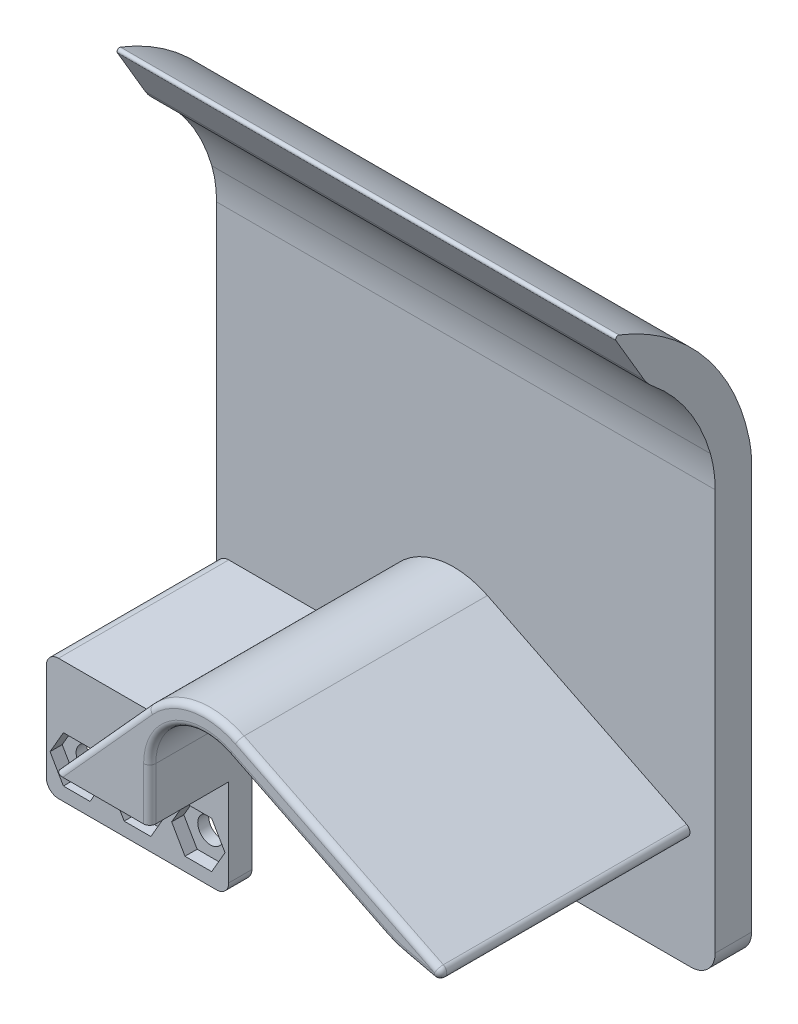
SolidWorks part; units mm, degrees
ref_plane "Front Plane" through (0, 0, 0) normal (0, 0, 1) x (1, 0, 0)
ref_plane "Top Plane" through (0, 0, 0) normal (0, 1, 0) x (1, 0, 0)
ref_plane "Right Plane" through (0, 0, 0) normal (1, 0, 0) x (0, 0, -1)
sketch "Sketch1" plane through (0, 0, 0) normal (0, 0, 1) x (1, 0, 0)
  line L0 (-31.75, -11.43) -> (-11.43, -11.43)
  line L1 (0, 0) -> (0, -50000) construction
  line L2 (-31.75, -11.43) -> (-11.7718, 10.6508)
  line L3 (31.75, -11.43) -> (11.7718, 10.6508)
  line L4 (-11.43, 0) -> (-11.43, -11.43)
  line L5 (11.43, 0) -> (11.43, -11.43)
  line L6 (11.43, -11.43) -> (31.75, -11.43)
  arc A0 (11.43, 0) -> (-11.43, 0) centre (0, 0) ccw
  arc A1 (11.7718, 10.6508) -> (-11.7718, 10.6508) centre (0, 0) ccw
  point P1 (0, 15.875)
  point P7 (0, -11.43)
  dimension "D1" = 22.86
  dimension "D2" = 31.75
  dimension "D3" = 63.5
extrude "Boss-Extrude1" add sketch "Sketch1" along normal blind 8.89
sketch "Sketch11" plane through (0, 0, 0) normal (0, 0, -1) x (-1, 0, 0)
  line L0 (11.7718, 10.6508) -> (31.75, -11.43) construction
  line L1 (31.75, -11.43) -> (11.43, -11.43) construction
  line L2 (11.43, -11.43) -> (11.43, 0) construction
  line L6 (27.1537, -6.35) -> (31.75, -11.43)
  line L7 (31.75, -11.43) -> (11.43, -11.43)
  line L13 (11.43, -6.35) -> (27.1537, -6.35)
  line L15 (11.43, -6.35) -> (11.43, -11.43)
  dimension "D1" = 5.08
extrude "Boss-Extrude2" add sketch "Sketch11" along normal blind 38.1
sketch "Sketch15" plane through (0, 0, 8.89) normal (0, 0, 1) x (1, 0, 0)
  line L1 (0, 22.5754) -> (41.9077, 22.5754)
  line L2 (0, 22.5754) -> (0, -20.5957)
  line L3 (0, -20.5957) -> (41.9077, -20.5957)
  line L4 (41.9077, 22.5754) -> (41.9077, -20.5957)
extrude "Cut-Extrude2" cut sketch "Sketch15" against normal blind 97.536
sketch "Sketch16" plane through (0, 0, 0) normal (0, 0, -1) x (-1, 0, 0)
  line L0 (11.7718, 10.6508) -> (27.1537, -6.35) construction
  line L1 (27.1537, -6.35) -> (11.43, -6.35) construction
  line L2 (0, 15.875) -> (0, 11.43) construction
  line L3 (11.7718, 10.6508) -> (27.1537, -6.35)
  line L4 (27.1537, -6.35) -> (11.43, -6.35)
  line L5 (0, 15.875) -> (0, 11.43)
  line L6 (11.43, -6.35) -> (11.43, 0)
  arc A0 (11.7718, 10.6508) -> (0, 15.875) centre (0, 0) ccw construction
  arc A1 (11.43, 0) -> (0, 11.43) centre (0, 0) ccw construction
  arc A2 (11.7718, 10.6508) -> (0, 15.875) centre (0, 0) ccw
  arc A3 (11.43, 0) -> (0, 11.43) centre (0, 0) ccw
extrude "Boss-Extrude5" add sketch "Sketch16" along normal blind 12.7
sketch "Sketch18" plane through (0, -6.35, 0) normal (0, 1, 0) x (1, 0, 0)
  line L0 (-11.43, 38.1) -> (-11.43, 12.7) construction
  line L1 (-11.43, 12.7) -> (-49.53, 12.7)
  line L2 (-11.43, 12.7) -> (-11.43, 38.1)
  line L3 (-11.43, 38.1) -> (-49.53, 38.1)
  line L4 (-49.53, 12.7) -> (-49.53, 38.1)
  line L5 (-27.1537, 38.1) -> (-11.43, 38.1) construction
  line L6 (-11.43, -8.89) -> (-11.43, 38.1) construction
  dimension "D1" = 38.1
extrude "Boss-Extrude6" add sketch "Sketch18" against normal up to surface (5.08 mm away) up to face at (-21.59, -11.43, -14.605)
sketch "Sketch17" plane through (0, -6.35, 0) normal (0, 1, 0) x (1, 0, 0)
  line L0 (-11.43, 38.1) -> (-11.43, 12.7) construction
  line L1 (-49.53, 38.1) -> (-11.43, 38.1) construction
  circle A0 centre (-15.24, 25.4) radius 2.0701
  circle A1 centre (-27.94, 25.4) radius 2.0701
  circle A2 centre (-40.64, 25.4) radius 2.0701
  dimension "D2" = 4.1402
  dimension "D1" = 3.81
  dimension "D3" = 12.7
  dimension "D4" = 3
sketch "Sketch19" plane through (0, 0, -38.1) normal (0, 0, -1) x (-1, 0, 0)
  line L1 (11.43, -6.35) -> (49.53, -6.35)
  line L2 (11.43, -6.35) -> (11.43, -31.75)
  line L3 (11.43, -31.75) -> (49.53, -31.75)
  line L4 (49.53, -6.35) -> (49.53, -31.75)
  dimension "D1" = 25.4
  dimension "D2" = 38.1
extrude "Boss-Extrude7" add sketch "Sketch19" along normal blind 5.08
extrude "Boss-Extrude9" add sketch "Sketch19<3>" against normal blind 5.08 from surface starting at face at (-39.4909, -8.89, -12.7)
sketch "Sketch19<3>" plane through (0, 0, -38.1) normal (0, 0, -1) x (-1, 0, 0) same geometry as "Sketch19"
sketch "Sketch20" plane through (0, 0, -43.18) normal (0, 0, -1) x (-1, 0, 0)
  line L0 (30.48, -6.35) -> (30.48, -31.75) construction
  line L1 (49.53, -6.35) -> (11.43, -6.35) construction
  line L2 (11.43, -31.75) -> (49.53, -31.75) construction
  line L4 (15.468, -24.13) -> (48.488, -24.13) construction
  line L7 (11.43, -11.43) -> (49.53, -11.43) construction
  circle A0 centre (30.48, -24.13) radius 2.667
  circle A1 centre (17.78, -24.13) radius 2.667
  circle A2 centre (43.18, -24.13) radius 2.667
  dimension "D1" = 12.7
  dimension "D3" = 5.334
  dimension "D2" = 12.7
  dimension "D4" = 12.7
extrude "Cut-Extrude3" cut sketch "Sketch20" against normal through all
extrude "Boss-Extrude10" add sketch "Sketch16<2>" along normal up to surface (43.18 mm away) up to face at (-45.847, -24.13, -43.18)
sketch "Sketch16<2>" plane through (0, 0, 0) normal (0, 0, -1) x (-1, 0, 0) same geometry as "Sketch16"
fillet "Fillet2" radius 2.54 6 edges at (-27.1537, -6.35, -25.4) (-49.53, -31.75, -40.64) (-11.43, -31.75, -40.64) (-49.53, -6.35, -25.4) (-11.43, -31.75, -10.16) (-49.53, -31.75, -10.16)
sketch "Sketch21" plane through (0, 0, -7.62) normal (0, 0, 1) x (1, 0, 0)
  line L0 (-27.6937, -19.304) -> (-33.2663, -19.304)
  line L1 (-40.3937, -19.304) -> (-45.9663, -19.304)
  line L2 (-45.9663, -19.304) -> (-48.7526, -24.13)
  line L3 (-48.7526, -24.13) -> (-45.9663, -28.956)
  line L4 (-45.9663, -28.956) -> (-40.3937, -28.956)
  line L5 (-40.3937, -28.956) -> (-37.6074, -24.13)
  line L6 (-37.6074, -24.13) -> (-40.3937, -19.304)
  line L7 (-33.2663, -19.304) -> (-36.0526, -24.13)
  line L8 (-36.0526, -24.13) -> (-33.2663, -28.956)
  line L9 (-33.2663, -28.956) -> (-27.6937, -28.956)
  line L10 (-27.6937, -28.956) -> (-24.9074, -24.13)
  line L11 (-24.9074, -24.13) -> (-27.6937, -19.304)
  line L12 (-14.9937, -19.304) -> (-20.5663, -19.304)
  line L13 (-20.5663, -19.304) -> (-23.3526, -24.13)
  line L14 (-23.3526, -24.13) -> (-20.5663, -28.956)
  line L15 (-20.5663, -28.956) -> (-14.9937, -28.956)
  line L16 (-14.9937, -28.956) -> (-12.2074, -24.13)
  line L17 (-12.2074, -24.13) -> (-14.9937, -19.304)
  circle A0 centre (-43.18, -24.13) radius 4.826 construction
  circle A1 centre (-30.48, -24.13) radius 4.826 construction
  circle A2 centre (-17.78, -24.13) radius 4.826 construction
  dimension "D1" = 9.652
  dimension "D3" = 12.7
  dimension "D2" = 3
extrude "Cut-Extrude4" cut sketch "Sketch21" against normal blind 2.54 from surface starting at face at (-40.513, -24.13, -7.62)
sketch "Sketch22" plane through (-49.53, 0, 0) normal (-1, 0, 0) x (0, 0, 1)
  line L0 (-38.354, -11.43) -> (-12.446, -11.43)
  line L1 (-12.446, -11.43) -> (-12.446, -35.8794)
  line L2 (-12.446, -35.8794) -> (-38.354, -35.8794)
  line L3 (-38.354, -35.8794) -> (-38.354, -11.43)
  line L4 (-38.1, -29.21) -> (-38.1, -11.43) construction
  line L5 (-12.7, -11.43) -> (-12.7, -29.21) construction
  line L6 (-7.62, -8.89) -> (-7.62, -29.21) construction
  line L7 (-7.62, -10.922) -> (14.1568, -10.922)
  line L8 (-7.62, -10.922) -> (-7.62, -15.4064)
  line L9 (-7.62, -15.4064) -> (14.1568, -15.4064)
  line L10 (14.1568, -10.922) -> (14.1568, -15.4064)
  line L11 (8.89, -11.43) -> (-7.62, -11.43) construction
  dimension "D1" = 0.254
  dimension "D2" = 0.254
  dimension "D3" = 0.508
extrude "Cut-Extrude5" cut sketch "Sketch22" against normal through all
sketch "Sketch23" plane through (0, 0, -43.18) normal (0, 0, -1) x (-1, 0, 0)
  line L0 (46.99, -31.75) -> (-54.61, -31.75)
  line L1 (13.97, -31.75) -> (46.99, -31.75) construction
  line L2 (-54.61, -31.75) -> (-54.61, 59.69)
  line L3 (-54.61, 59.69) -> (49.53, 59.69)
  line L4 (49.53, 59.69) -> (49.53, -29.21)
  line L5 (49.53, -29.21) -> (49.53, -8.89) construction
  arc A0 (46.99, -31.75) -> (49.53, -29.21) centre (46.99, -29.21) ccw
  arc A1 (46.99, -31.75) -> (49.53, -29.21) centre (46.99, -29.21) ccw construction
  circle A2 centre (17.78, -24.13) radius 2.667
  circle A3 centre (30.48, -24.13) radius 2.667
  circle A4 centre (43.18, -24.13) radius 2.667
  dimension "D1" = 88.9
  dimension "D2" = 101.6
extrude "Boss-Extrude11" add sketch "Sketch23" along normal blind 7.62
fillet "Fillet3" radius 5.08 1 edges at (54.61, -31.75, -46.99)
sketch "Sketch24" plane through (0, 0, 8.89) normal (0, 0, 1) x (1, 0, 0)
  line L0 (5.0678, 10.2451) -> (39.588, -6.8304)
  line L1 (7.0386, 14.2293) -> (58.3876, -11.1707)
  line L2 (58.3876, -11.1707) -> (39.588, -6.8304)
  line L3 (0, 11.43) -> (0, 15.875)
  line L5 (-11.43, -10.922) -> (-31.2904, -10.922) construction
  arc A0 (0, 11.43) -> (5.0678, 10.2451) centre (0, 0) cw
  arc A1 (0, 15.875) -> (7.0386, 14.2293) centre (0, 0) cw
  dimension "D1" = 25.4
  dimension "D2" = 13
extrude "Boss-Extrude12" add sketch "Sketch24" against normal up to surface (52.07 mm away) up to face at (-6.5972, 0.9439, -43.18)
fillet "Fillet4" radius 1.27 1 edges at (58.3876, -11.1707, -17.145)
fillet "Fillet5" radius 20.32 1 edges at (39.588, -6.8304, -17.145)
sketch "Sketch25" plane through (-49.53, 0, 0) normal (-1, 0, 0) x (0, 0, 1)
  line L0 (-29.0281, 83.304) -> (-21.7408, 95.6935)
  line L11 (-38.354, -29.21) -> (-38.354, -11.43)
  line L12 (-38.354, -11.43) -> (-12.446, -11.43)
  line L13 (-12.446, -11.43) -> (-12.446, -29.21)
  line L14 (-12.446, -29.21) -> (-7.62, -29.21)
  line L15 (-7.62, -29.21) -> (-7.62, -8.89)
  line L16 (-7.62, -8.89) -> (-43.18, -8.89)
  line L17 (-43.18, -8.89) -> (-43.18, 59.69)
  line L18 (-43.18, 59.69) -> (-50.8, 59.69)
  line L19 (-50.8, 59.69) -> (-50.8, -29.21)
  line L20 (-50.8, -29.21) -> (-38.354, -29.21)
  line L28 (-43.18, 59.69) -> (-50.8, 59.69)
  arc A0 (-43.18, 59.69) -> (-29.0281, 83.304) centre (-6.9422, 54.0204) cw
  arc A1 (-50.8, 59.69) -> (-21.7408, 95.6935) centre (-6.9422, 54.0204) cw
  dimension "D1" = 0
extrude "Boss-Extrude13" add sketch "Sketch25" against normal up to surface (104.14 mm away) up to face at (54.61, 16.51, -46.99)
fillet "Fillet6" radius 0.508 1 edges at (2.54, 95.6935, -21.7408)
fillet "Fillet7" radius 7.62 1 edges at (2.54, 83.304, -29.0281)
fillet "Fillet8" radius 25.4 2 edges at (2.54, 59.69, -50.8) (2.54, 59.69, -43.18)
fillet "Fillet9" radius 1.27 9 edges at (-11.43, -5.461, 8.89) (-6.0299, 9.71, 8.89) (21.2646, 2.2333, 8.89) (39.6344, -6.7004, 8.89) (44.8446, -8.044, 8.89) (49.2711, -7.9137, 8.89) (27.8384, 3.9406, 8.89) (-21.5311, -0.1356, 8.89) (-2.9669, 15.5953, 8.89)
